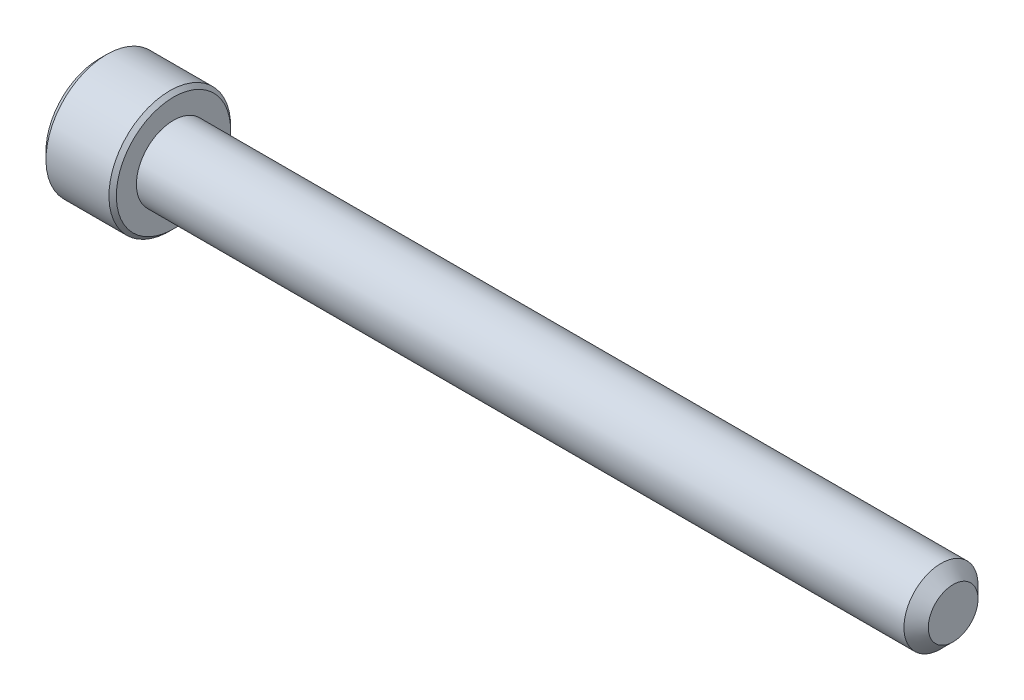
SolidWorks part; units mm, degrees
ref_plane "Front Plane" through (0, 0, 0) normal (0, 0, 1) x (1, 0, 0)
ref_plane "Top Plane" through (0, 0, 0) normal (0, 1, 0) x (1, 0, 0)
ref_plane "Right Plane" through (0, 0, 0) normal (1, 0, 0) x (0, 0, -1)
sketch "Sketch1" plane through (0, 0, 0) normal (0, 0, 1) x (1, 0, 0)
  line L0 (25.4, 0) -> (-25.4, 0) construction
  line L1 (25.4, 2.413) -> (25.4, -2.413) construction
  line L2 (-25.4, 3.7211) -> (-25.4, -3.7211) construction
  line L3 (-25.6413, 3.9624) -> (-29.7434, 3.9624) construction
  line L4 (-29.7434, 3.9624) -> (-30.226, 3.4798) construction
  line L5 (-30.226, 3.4798) -> (-30.226, -3.4798) construction
  line L6 (-30.226, -3.4798) -> (-29.7434, -3.9624) construction
  line L7 (-29.7434, -3.9624) -> (-25.6413, -3.9624) construction
  line L8 (-25.6413, 3.9624) -> (-25.4, 3.7211) construction
  line L9 (-25.4, -3.7211) -> (-25.6413, -3.9624) construction
  point P5 (-25.4, 3.9624)
  point P6 (-25.4, -3.9624)
  point P7 (-27.94, 0)
  point P12 (21.1667, -2.413)
  dimension "D1" = 45
  dimension "Dec." = 4.826
  dimension "Length" = 50.8
  dimension "Head Dia" = 7.9248
  dimension "Head Height" = 4.826
  dimension "Hex Depth" = 2.286
  dimension "Chamfer" = 0.4826
  dimension "D2" = 4.2333
  dimension "D3" = 0.2413
  dimension "D4" = 45
ref_plane "Plane1" through (25.4, 0, 0) normal (1, 0, 0) x (0, 0, -1)
ref_plane "Plane2" through (-30.226, 0, 0) normal (1, 0, 0) x (0, 0, -1)
sketch "Sketch2" plane through (25.4, 0, 0) normal (1, 0, 0) x (0, 0, -1)
  circle A0 centre (0, 0) radius 2.413
extrude "Boss-Extrude1" add sketch "Sketch2" against normal up to vertex (50.8 mm away) up to point (-25.4, 0, 0)
sketch "Sketch3" plane through (25.4, 0, 0) normal (1, 0, 0) x (0, 0, -1)
  circle A0 centre (0, 0) radius 2.413 construction
  circle A1 centre (0, 0) radius 2.413
curve "Helix/Spiral1" [suppressed] pitch 1.0583 height 51.8583 turns 49 parameters "Pitch"=1.0583
chamfer "Chamfer1" distance 0.7937 angle 45 1 edges at (25.4, 0, -2.413)
sketch "Sketch5" plane through (0, 0, 0) normal (0, 0, 1) x (1, 0, 0)
  line L0 (24.937, 2.413) -> (25.863, 2.413)
  line L1 (25.863, 2.413) -> (25.4661, 1.7256)
  line L2 (25.4661, 1.7256) -> (25.3339, 1.7256)
  line L3 (25.3339, 1.7256) -> (24.937, 2.413)
  line L4 (25.4, 1.7256) -> (25.4, 2.413) construction
  line L5 (25.1354, 2.0693) -> (25.6646, 2.0693) construction
  dimension "D1" = 60
  dimension "D2" = 0.5292
  dimension "D3" = 0.1323
sweep "Cut-Sweep1" [suppressed] cut profiles "Sketch5" path "Helix/Spiral1"
sketch "Sketch4" plane through (-30.226, 0, 0) normal (1, 0, 0) x (0, 0, -1)
  line L0 (-3.9624, 0.7937) -> (3.9624, 0.7937) construction
  line L1 (0, 2.2877) -> (-1.9812, 1.1438)
  line L2 (-1.9812, 1.1438) -> (-1.9812, -1.1438)
  line L3 (-1.9812, -1.1438) -> (0, -2.2877)
  line L4 (0, -2.2877) -> (1.9812, -1.1438)
  line L5 (1.9812, -1.1438) -> (1.9812, 1.1438)
  line L6 (1.9812, 1.1438) -> (0, 2.2877)
  line L7 (0, 0) -> (0, 0.7937) construction
  circle A0 centre (0, 0) radius 1.9812 construction
  dimension "Hex Size" = 3.9624
  dimension "D1" = 7.9248
  dimension "D2" = 0.7937
sketch "Sketch6" plane through (0, 0, 0) normal (0, 0, 1) x (1, 0, 0)
  line L0 (-29.7434, 3.9624) -> (-30.226, 3.4798) construction
  line L2 (-25.4, 3.7211) -> (-25.4, -3.7211) construction
  line L3 (-30.226, 3.4798) -> (-30.226, -3.4798) construction
  line L4 (-29.7434, 3.9624) -> (-30.226, 3.4798)
  line L5 (-25.6413, 3.9624) -> (-29.7434, 3.9624) construction
  line L6 (-25.4, 3.7211) -> (-25.4, 0)
  line L7 (-30.226, 3.4798) -> (-30.226, 0)
  line L8 (-25.4, 0) -> (-30.226, 0) construction
  line L9 (-25.4, 0) -> (-30.226, 0)
  line L10 (-25.6413, 3.9624) -> (-25.4, 3.7211) construction
  line L11 (-25.6413, 3.9624) -> (-29.7434, 3.9624)
  line L12 (-25.6413, 3.9624) -> (-25.4, 3.7211)
revolve "Revolve1" add sketch "Sketch6" angle 360 about L8
extrude "Cut-Extrude1" cut sketch "Sketch4" along normal up to vertex (2.286 mm away) up to point (-27.94, 0, 0)
sketch "Sketch8" plane through (-30.226, 0, 0) normal (-1, 0, 0) x (0, 0, 1)
  circle A1 centre (0, 0) radius 2.2877
extrude "Cut-Extrude2" cut sketch "Sketch8" against normal blind 0.9652 draft 45
equation "\"D3@Helix/Spiral1\" = \"Length@Sketch1\"+\"Pitch@Helix/Spiral1\""
equation "\"D3@Sketch5\" = \"Pitch@Helix/Spiral1\"*.125"
equation "\"D2@Sketch5\" = \"Pitch@Helix/Spiral1\"*.50"
equation "\"D1@Chamfer1\" = \"Pitch@Helix/Spiral1\"*.75"
equation "\"D2@Sketch1\" = \"Pitch@Helix/Spiral1\"*4"
equation "\"D1@Sketch4\" = \"Head Dia@Sketch1\""
equation "\"Chamfer@Sketch1\" = \"Head Height@Sketch1\"/10"
equation "\"D3@Sketch1\" = \"Chamfer@Sketch1\"/2"
equation "\"D1@Cut-Extrude2\" = \"Chamfer@Sketch1\"*2"
